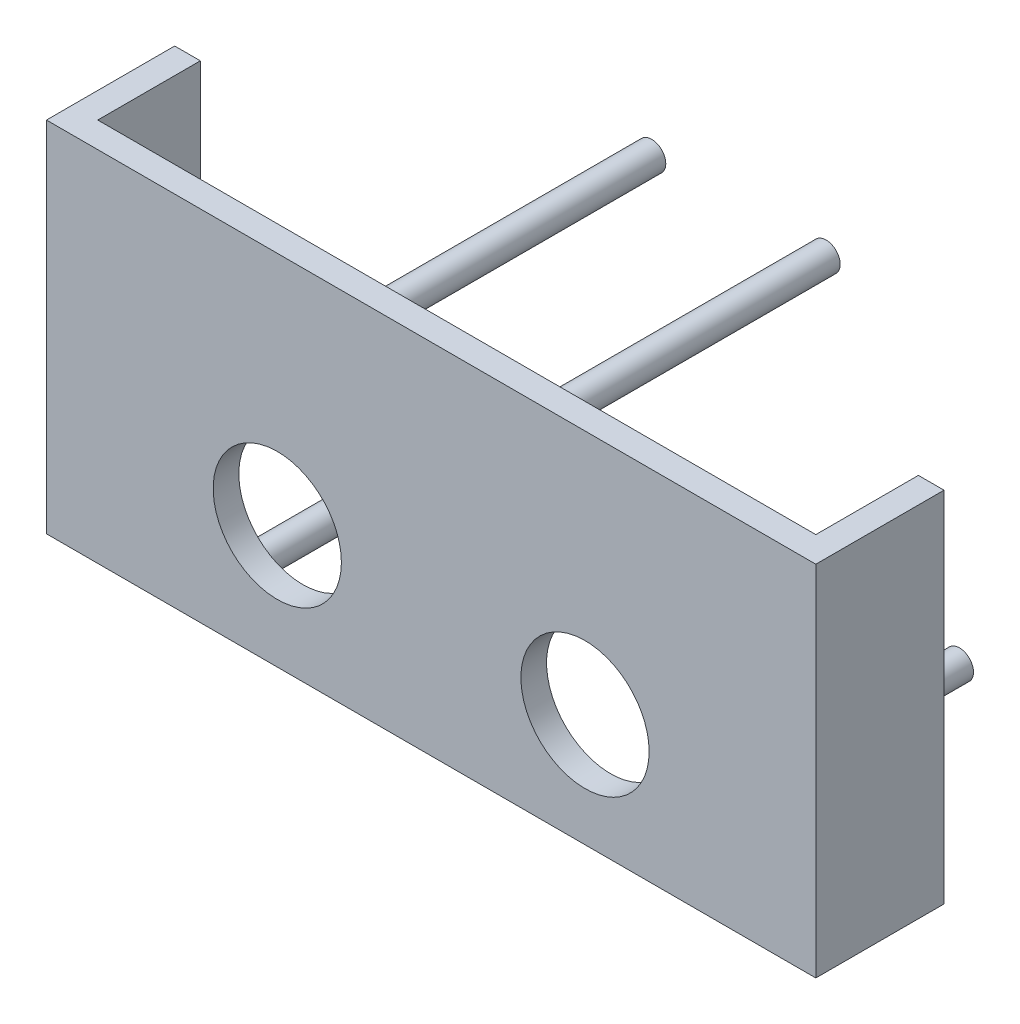
SolidWorks part; units mm, degrees
ref_plane "Plan de face" through (0, 0, 0) normal (0, 0, 1) x (1, 0, 0)
ref_plane "Plan de dessus" through (0, 0, 0) normal (0, 1, 0) x (1, 0, 0)
ref_plane "Plan de droite" through (0, 0, 0) normal (1, 0, 0) x (0, 0, -1)
sketch "Esquisse1" plane through (0, 0, 0) normal (0, 0, 1) x (1, 0, 0)
  line L1 (0, 0) -> (-100, 0)
  line L2 (0, 0) -> (0, 69.87)
  line L3 (0, 69.87) -> (-100, 69.87)
  line L4 (-100, 0) -> (-100, 69.87)
  dimension "D1" = 69.87
  dimension "D2" = 100
extrude "Boss.-Extru.1" add sketch "Esquisse1" along normal blind 5
sketch "Esquisse2" plane through (0, 0, 5) normal (0, 0, 1) x (1, 0, 0)
  line L0 (-100, 0) -> (0, 0) construction
  line L3 (0, 0) -> (0, 69.87) construction
  line L4 (-100, 69.87) -> (-100, 0) construction
  line L5 (-60, 69.87) -> (-60, 0)
  line L6 (0, 69.87) -> (-100, 69.87) construction
  line L7 (-40, 69.87) -> (-40, 0)
  line L8 (0, 0) -> (0, 69.87) construction
  circle A0 centre (-7, 7) radius 2.75
  circle A1 centre (-33, 62.87) radius 2.75
  circle A2 centre (-67, 62.87) radius 2.75
  circle A3 centre (-93, 7) radius 2.75
  circle A4 centre (-80, 23.9131) radius 12.5
  circle A5 centre (-20, 21.9808) radius 12.5
  point P20 (0, 34.935)
  point P27 (-100, 34.935)
  dimension "D1" = 5.5
  dimension "D2" = 5.5
  dimension "D3" = 5.5
  dimension "D4" = 5.5
  dimension "D15" = 25
  dimension "D16" = 25
  dimension "D5" = 7
  dimension "D6" = 7
  dimension "D7" = 7
  dimension "D8" = 7
  dimension "D9" = 40
  dimension "D10" = 40
  dimension "D11" = 7
  dimension "D12" = 7
  dimension "D13" = 7
  dimension "D14" = 7
  dimension "D17" = 20
  dimension "D18" = 20
extrude "Enlèv. mat.-Extru.1" cut sketch "Esquisse2" against normal blind 5 contours A4 | A5 region at (-80, 23.9131, 5) region at (-20, 21.9808, 5)
sketch "Esquisse3" plane through (0, 0, 5) normal (0, 0, 1) x (1, 0, 0)
  line L1 (-100, 69.87) -> (-125, 69.87)
  line L2 (-100, 69.87) -> (-100, 0)
  line L3 (-100, 0) -> (-125, 0)
  line L4 (-125, 69.87) -> (-125, 0)
  line L5 (0, 69.87) -> (25, 69.87)
  line L6 (0, 69.87) -> (0, 0)
  line L7 (0, 0) -> (25, 0)
  line L8 (25, 69.87) -> (25, 0)
  dimension "D1" = 25
  dimension "D2" = 25
extrude "Boss.-Extru.2" add sketch "Esquisse3" against normal blind 5
sketch "Esquisse4" plane through (0, 0, 0) normal (0, 0, -1) x (-1, 0, 0)
  line L0 (125, 0) -> (-25, 0) construction
  line L1 (125, 69.87) -> (120, 69.87)
  line L2 (125, 69.87) -> (125, 0)
  line L3 (125, 0) -> (120, 0)
  line L4 (120, 69.87) -> (120, 0)
  line L5 (-25, 69.87) -> (125, 69.87) construction
  line L6 (-25, 69.87) -> (-20, 69.87)
  line L7 (-25, 69.87) -> (-25, 0)
  line L8 (-25, 0) -> (-20, 0)
  line L9 (-20, 69.87) -> (-20, 0)
  line L10 (-25, 0) -> (-25, 69.87) construction
  dimension "D1" = 5
  dimension "D2" = 5
extrude "Boss.-Extru.3" add sketch "Esquisse4" along normal blind 20
extrude "Boss.-Extru.4" add sketch "Esquisse2<3>" against normal blind 60 contours A2
sketch "Esquisse2<3>" plane through (0, 0, 5) normal (0, 0, 1) x (1, 0, 0) same geometry as "Esquisse2"
extrude "Boss.-Extru.5" add sketch "Esquisse2<4>" against normal blind 60 contours A1
sketch "Esquisse2<4>" plane through (0, 0, 5) normal (0, 0, 1) x (1, 0, 0) same geometry as "Esquisse2"
extrude "Boss.-Extru.6" add sketch "Esquisse2<5>" against normal blind 60 contours A3
sketch "Esquisse2<5>" plane through (0, 0, 5) normal (0, 0, 1) x (1, 0, 0) same geometry as "Esquisse2"
extrude "Boss.-Extru.7" add sketch "Esquisse2<6>" against normal blind 60 contours A0
sketch "Esquisse2<6>" plane through (0, 0, 5) normal (0, 0, 1) x (1, 0, 0) same geometry as "Esquisse2"
